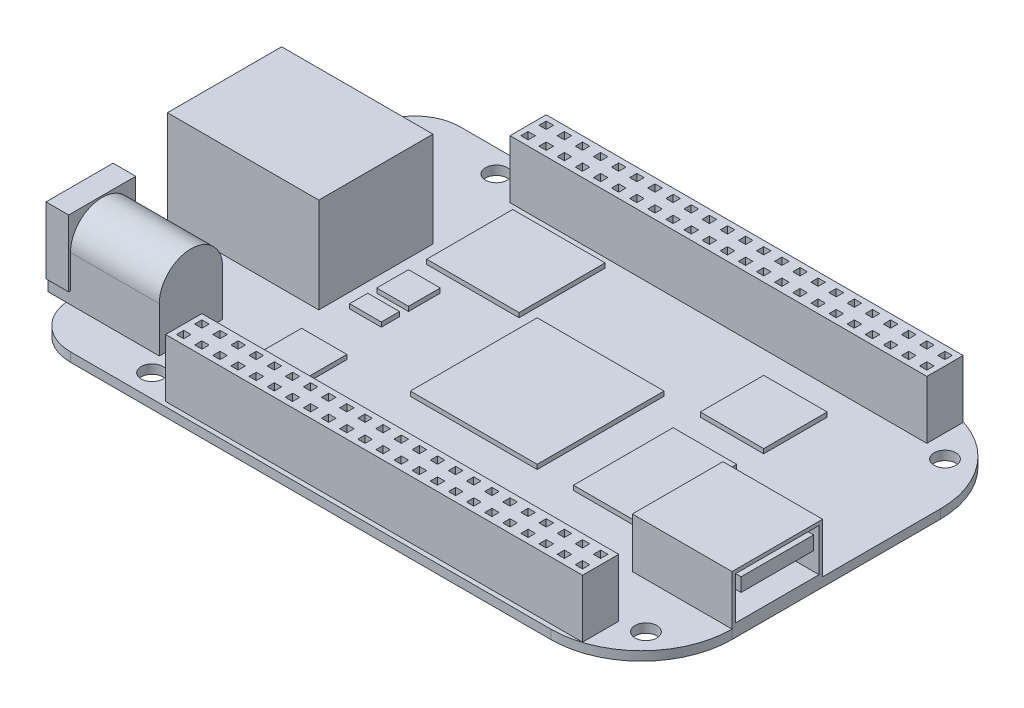
SolidWorks part; units mm, degrees
material "ABS"
ref_plane "Front Plane" through (0, 0, 0) normal (0, 0, 1) x (1, 0, 0)
ref_plane "Top Plane" through (0, 0, 0) normal (0, 1, 0) x (1, 0, 0)
ref_plane "Right Plane" through (0, 0, 0) normal (1, 0, 0) x (0, 0, -1)
sketch "Sketch1" plane through (0, 0, 0) normal (0, 1, 0) x (1, 0, 0)
  line L1 (-12.7, 0) -> (-80.01, 0)
  line L2 (0, 12.7) -> (0, 41.91)
  line L3 (-12.7, 54.61) -> (-80.01, 54.61)
  line L4 (-86.36, 6.35) -> (-86.36, 48.26)
  arc A0 (0, 12.7) -> (-12.7, 0) centre (-12.7, 12.7) cw
  arc A1 (0, 41.91) -> (-12.7, 54.61) centre (-12.7, 41.91) ccw
  arc A2 (-86.36, 6.35) -> (-80.01, 0) centre (-80.01, 6.35) ccw
  arc A3 (-86.36, 48.26) -> (-80.01, 54.61) centre (-80.01, 48.26) cw
  point P7 (0, 0)
  point P10 (0, 54.61)
  point P13 (-86.36, 0)
  dimension "D3" = 12.7
  dimension "D4" = 6.35
  dimension "D1" = 86.36
  dimension "D2" = 54.61
extrude "Boss-Extrude1" add sketch "Sketch1" along normal blind 1.27
sketch "Sketch2" plane through (0, 1.27, 0) normal (0, 1, 0) x (1, 0, 0)
  line L0 (-80.01, 0) -> (-12.7, 0) construction
  line L2 (-71.755, 51.435) -> (-71.755, 3.175) construction
  line L3 (-86.36, 48.26) -> (-86.36, 6.35) construction
  line L4 (-5.715, 48.26) -> (-5.715, 6.35) construction
  circle A0 centre (-71.755, 51.435) radius 1.524
  circle A1 centre (-71.755, 3.175) radius 1.524
  circle A2 centre (-5.715, 48.26) radius 1.524
  circle A3 centre (-5.715, 6.35) radius 1.524
  dimension "D7" = 3.048
  dimension "D1" = 48.26
  dimension "D2" = 41.91
  dimension "D3" = 6.35
  dimension "D4" = 14.605
  dimension "D5" = 80.645
  dimension "D6" = 3.175
extrude "Cut-Extrude1" cut sketch "Sketch2" along direction (0, -1, 0) on the side against the normal up to surface (1.27 mm away) up to face at (-44.4387, 0, -27.305)
sketch "Sketch3" plane through (0, 1.27, 0) normal (0, 1, 0) x (1, 0, 0)
  line L0 (-10.16, 48.895) -> (-10.16, 50.165) construction
  line L1 (-67.31, 53.975) -> (-8.89, 53.975)
  line L2 (-67.31, 53.975) -> (-67.31, 48.895)
  line L3 (-67.31, 48.895) -> (-8.89, 48.895)
  line L4 (-8.89, 53.975) -> (-8.89, 48.895)
  line L5 (-86.36, 27.305) -> (0, 27.305) construction
  line L6 (0, 12.7) -> (0, 41.91) construction
  line L7 (-66.548, 4.953) -> (-66.548, 3.937)
  line L8 (-66.548, 4.953) -> (-65.532, 4.953)
  line L9 (-10.16, 50.165) -> (-10.16, 52.705) construction
  line L10 (-10.16, 52.705) -> (-10.16, 53.975) construction
  line L11 (-13.208, 52.197) -> (-12.192, 52.197)
  line L12 (-10.668, 53.213) -> (-9.652, 53.213)
  line L13 (-10.668, 53.213) -> (-10.668, 52.197)
  line L14 (-10.668, 52.197) -> (-9.652, 52.197)
  line L15 (-9.652, 53.213) -> (-9.652, 52.197)
  line L16 (-10.668, 53.213) -> (-9.652, 52.197) construction
  line L17 (-10.668, 52.197) -> (-9.652, 53.213) construction
  line L18 (-10.668, 49.657) -> (-9.652, 49.657)
  line L19 (-10.668, 49.657) -> (-10.668, 50.673)
  line L20 (-10.668, 50.673) -> (-9.652, 50.673)
  line L21 (-9.652, 49.657) -> (-9.652, 50.673)
  line L22 (-10.668, 49.657) -> (-9.652, 50.673) construction
  line L23 (-10.668, 50.673) -> (-9.652, 49.657) construction
  line L24 (-13.208, 53.213) -> (-13.208, 52.197)
  line L25 (-13.208, 53.213) -> (-12.192, 53.213)
  line L26 (-12.192, 53.213) -> (-12.192, 52.197)
  line L27 (-13.208, 50.673) -> (-12.192, 50.673)
  line L28 (-12.192, 49.657) -> (-12.192, 50.673)
  line L29 (-13.208, 49.657) -> (-12.192, 49.657)
  line L30 (-13.208, 49.657) -> (-13.208, 50.673)
  line L31 (-15.748, 52.197) -> (-14.732, 52.197)
  line L32 (-15.748, 53.213) -> (-15.748, 52.197)
  line L33 (-15.748, 53.213) -> (-14.732, 53.213)
  line L34 (-14.732, 53.213) -> (-14.732, 52.197)
  line L35 (-15.748, 50.673) -> (-14.732, 50.673)
  line L36 (-14.732, 49.657) -> (-14.732, 50.673)
  line L37 (-15.748, 49.657) -> (-14.732, 49.657)
  line L38 (-15.748, 49.657) -> (-15.748, 50.673)
  line L39 (-18.288, 52.197) -> (-17.272, 52.197)
  line L40 (-18.288, 53.213) -> (-18.288, 52.197)
  line L41 (-18.288, 53.213) -> (-17.272, 53.213)
  line L42 (-17.272, 53.213) -> (-17.272, 52.197)
  line L43 (-18.288, 50.673) -> (-17.272, 50.673)
  line L44 (-17.272, 49.657) -> (-17.272, 50.673)
  line L45 (-18.288, 49.657) -> (-17.272, 49.657)
  line L46 (-18.288, 49.657) -> (-18.288, 50.673)
  line L47 (-20.828, 52.197) -> (-19.812, 52.197)
  line L48 (-20.828, 53.213) -> (-20.828, 52.197)
  line L49 (-20.828, 53.213) -> (-19.812, 53.213)
  line L50 (-19.812, 53.213) -> (-19.812, 52.197)
  line L51 (-20.828, 50.673) -> (-19.812, 50.673)
  line L52 (-19.812, 49.657) -> (-19.812, 50.673)
  line L53 (-20.828, 49.657) -> (-19.812, 49.657)
  line L54 (-20.828, 49.657) -> (-20.828, 50.673)
  line L55 (-23.368, 52.197) -> (-22.352, 52.197)
  line L56 (-23.368, 53.213) -> (-23.368, 52.197)
  line L57 (-23.368, 53.213) -> (-22.352, 53.213)
  line L58 (-22.352, 53.213) -> (-22.352, 52.197)
  line L59 (-23.368, 50.673) -> (-22.352, 50.673)
  line L60 (-22.352, 49.657) -> (-22.352, 50.673)
  line L61 (-23.368, 49.657) -> (-22.352, 49.657)
  line L62 (-23.368, 49.657) -> (-23.368, 50.673)
  line L63 (-25.908, 52.197) -> (-24.892, 52.197)
  line L64 (-25.908, 53.213) -> (-25.908, 52.197)
  line L65 (-25.908, 53.213) -> (-24.892, 53.213)
  line L66 (-24.892, 53.213) -> (-24.892, 52.197)
  line L67 (-25.908, 50.673) -> (-24.892, 50.673)
  line L68 (-24.892, 49.657) -> (-24.892, 50.673)
  line L69 (-25.908, 49.657) -> (-24.892, 49.657)
  line L70 (-25.908, 49.657) -> (-25.908, 50.673)
  line L71 (-28.448, 52.197) -> (-27.432, 52.197)
  line L72 (-28.448, 53.213) -> (-28.448, 52.197)
  line L73 (-28.448, 53.213) -> (-27.432, 53.213)
  line L74 (-27.432, 53.213) -> (-27.432, 52.197)
  line L75 (-28.448, 50.673) -> (-27.432, 50.673)
  line L76 (-27.432, 49.657) -> (-27.432, 50.673)
  line L77 (-28.448, 49.657) -> (-27.432, 49.657)
  line L78 (-28.448, 49.657) -> (-28.448, 50.673)
  line L79 (-30.988, 52.197) -> (-29.972, 52.197)
  line L80 (-30.988, 53.213) -> (-30.988, 52.197)
  line L81 (-30.988, 53.213) -> (-29.972, 53.213)
  line L82 (-29.972, 53.213) -> (-29.972, 52.197)
  line L83 (-30.988, 50.673) -> (-29.972, 50.673)
  line L84 (-29.972, 49.657) -> (-29.972, 50.673)
  line L85 (-30.988, 49.657) -> (-29.972, 49.657)
  line L86 (-30.988, 49.657) -> (-30.988, 50.673)
  line L87 (-33.528, 52.197) -> (-32.512, 52.197)
  line L88 (-33.528, 53.213) -> (-33.528, 52.197)
  line L89 (-33.528, 53.213) -> (-32.512, 53.213)
  line L90 (-32.512, 53.213) -> (-32.512, 52.197)
  line L91 (-33.528, 50.673) -> (-32.512, 50.673)
  line L92 (-32.512, 49.657) -> (-32.512, 50.673)
  line L93 (-33.528, 49.657) -> (-32.512, 49.657)
  line L94 (-33.528, 49.657) -> (-33.528, 50.673)
  line L95 (-36.068, 52.197) -> (-35.052, 52.197)
  line L96 (-36.068, 53.213) -> (-36.068, 52.197)
  line L97 (-36.068, 53.213) -> (-35.052, 53.213)
  line L98 (-35.052, 53.213) -> (-35.052, 52.197)
  line L99 (-36.068, 50.673) -> (-35.052, 50.673)
  line L100 (-35.052, 49.657) -> (-35.052, 50.673)
  line L101 (-36.068, 49.657) -> (-35.052, 49.657)
  line L102 (-36.068, 49.657) -> (-36.068, 50.673)
  line L103 (-38.608, 52.197) -> (-37.592, 52.197)
  line L104 (-38.608, 53.213) -> (-38.608, 52.197)
  line L105 (-38.608, 53.213) -> (-37.592, 53.213)
  line L106 (-37.592, 53.213) -> (-37.592, 52.197)
  line L107 (-38.608, 50.673) -> (-37.592, 50.673)
  line L108 (-37.592, 49.657) -> (-37.592, 50.673)
  line L109 (-38.608, 49.657) -> (-37.592, 49.657)
  line L110 (-38.608, 49.657) -> (-38.608, 50.673)
  line L111 (-41.148, 52.197) -> (-40.132, 52.197)
  line L112 (-41.148, 53.213) -> (-41.148, 52.197)
  line L113 (-41.148, 53.213) -> (-40.132, 53.213)
  line L114 (-40.132, 53.213) -> (-40.132, 52.197)
  line L115 (-41.148, 50.673) -> (-40.132, 50.673)
  line L116 (-40.132, 49.657) -> (-40.132, 50.673)
  line L117 (-41.148, 49.657) -> (-40.132, 49.657)
  line L118 (-41.148, 49.657) -> (-41.148, 50.673)
  line L119 (-43.688, 52.197) -> (-42.672, 52.197)
  line L120 (-43.688, 53.213) -> (-43.688, 52.197)
  line L121 (-43.688, 53.213) -> (-42.672, 53.213)
  line L122 (-42.672, 53.213) -> (-42.672, 52.197)
  line L123 (-43.688, 50.673) -> (-42.672, 50.673)
  line L124 (-42.672, 49.657) -> (-42.672, 50.673)
  line L125 (-43.688, 49.657) -> (-42.672, 49.657)
  line L126 (-43.688, 49.657) -> (-43.688, 50.673)
  line L127 (-46.228, 52.197) -> (-45.212, 52.197)
  line L128 (-46.228, 53.213) -> (-46.228, 52.197)
  line L129 (-46.228, 53.213) -> (-45.212, 53.213)
  line L130 (-45.212, 53.213) -> (-45.212, 52.197)
  line L131 (-46.228, 50.673) -> (-45.212, 50.673)
  line L132 (-45.212, 49.657) -> (-45.212, 50.673)
  line L133 (-46.228, 49.657) -> (-45.212, 49.657)
  line L134 (-46.228, 49.657) -> (-46.228, 50.673)
  line L135 (-48.768, 52.197) -> (-47.752, 52.197)
  line L136 (-48.768, 53.213) -> (-48.768, 52.197)
  line L137 (-48.768, 53.213) -> (-47.752, 53.213)
  line L138 (-47.752, 53.213) -> (-47.752, 52.197)
  line L139 (-48.768, 50.673) -> (-47.752, 50.673)
  line L140 (-47.752, 49.657) -> (-47.752, 50.673)
  line L141 (-48.768, 49.657) -> (-47.752, 49.657)
  line L142 (-48.768, 49.657) -> (-48.768, 50.673)
  line L143 (-51.308, 52.197) -> (-50.292, 52.197)
  line L144 (-51.308, 53.213) -> (-51.308, 52.197)
  line L145 (-51.308, 53.213) -> (-50.292, 53.213)
  line L146 (-50.292, 53.213) -> (-50.292, 52.197)
  line L147 (-51.308, 50.673) -> (-50.292, 50.673)
  line L148 (-50.292, 49.657) -> (-50.292, 50.673)
  line L149 (-51.308, 49.657) -> (-50.292, 49.657)
  line L150 (-51.308, 49.657) -> (-51.308, 50.673)
  line L151 (-53.848, 52.197) -> (-52.832, 52.197)
  line L152 (-53.848, 53.213) -> (-53.848, 52.197)
  line L153 (-53.848, 53.213) -> (-52.832, 53.213)
  line L154 (-52.832, 53.213) -> (-52.832, 52.197)
  line L155 (-53.848, 50.673) -> (-52.832, 50.673)
  line L156 (-52.832, 49.657) -> (-52.832, 50.673)
  line L157 (-53.848, 49.657) -> (-52.832, 49.657)
  line L158 (-53.848, 49.657) -> (-53.848, 50.673)
  line L159 (-56.388, 52.197) -> (-55.372, 52.197)
  line L160 (-56.388, 53.213) -> (-56.388, 52.197)
  line L161 (-56.388, 53.213) -> (-55.372, 53.213)
  line L162 (-55.372, 53.213) -> (-55.372, 52.197)
  line L163 (-56.388, 50.673) -> (-55.372, 50.673)
  line L164 (-55.372, 49.657) -> (-55.372, 50.673)
  line L165 (-56.388, 49.657) -> (-55.372, 49.657)
  line L166 (-56.388, 49.657) -> (-56.388, 50.673)
  line L167 (-58.928, 52.197) -> (-57.912, 52.197)
  line L168 (-58.928, 53.213) -> (-58.928, 52.197)
  line L169 (-58.928, 53.213) -> (-57.912, 53.213)
  line L170 (-57.912, 53.213) -> (-57.912, 52.197)
  line L171 (-58.928, 50.673) -> (-57.912, 50.673)
  line L172 (-57.912, 49.657) -> (-57.912, 50.673)
  line L173 (-58.928, 49.657) -> (-57.912, 49.657)
  line L174 (-58.928, 49.657) -> (-58.928, 50.673)
  line L175 (-61.468, 52.197) -> (-60.452, 52.197)
  line L176 (-61.468, 53.213) -> (-61.468, 52.197)
  line L177 (-61.468, 53.213) -> (-60.452, 53.213)
  line L178 (-60.452, 53.213) -> (-60.452, 52.197)
  line L179 (-61.468, 50.673) -> (-60.452, 50.673)
  line L180 (-60.452, 49.657) -> (-60.452, 50.673)
  line L181 (-61.468, 49.657) -> (-60.452, 49.657)
  line L182 (-61.468, 49.657) -> (-61.468, 50.673)
  line L183 (-64.008, 52.197) -> (-62.992, 52.197)
  line L184 (-64.008, 53.213) -> (-64.008, 52.197)
  line L185 (-64.008, 53.213) -> (-62.992, 53.213)
  line L186 (-62.992, 53.213) -> (-62.992, 52.197)
  line L187 (-64.008, 50.673) -> (-62.992, 50.673)
  line L188 (-62.992, 49.657) -> (-62.992, 50.673)
  line L189 (-64.008, 49.657) -> (-62.992, 49.657)
  line L190 (-64.008, 49.657) -> (-64.008, 50.673)
  line L191 (-66.548, 52.197) -> (-65.532, 52.197)
  line L192 (-66.548, 53.213) -> (-66.548, 52.197)
  line L193 (-66.548, 53.213) -> (-65.532, 53.213)
  line L194 (-65.532, 53.213) -> (-65.532, 52.197)
  line L195 (-66.548, 50.673) -> (-65.532, 50.673)
  line L196 (-65.532, 49.657) -> (-65.532, 50.673)
  line L197 (-66.548, 49.657) -> (-65.532, 49.657)
  line L198 (-66.548, 49.657) -> (-66.548, 50.673)
  line L199 (-66.548, 49.657) -> (-65.532, 50.673) construction
  line L200 (-86.36, 48.26) -> (-86.36, 6.35) construction
  line L201 (-65.532, 4.953) -> (-65.532, 3.937)
  line L202 (-12.7, 54.61) -> (-80.01, 54.61) construction
  line L203 (-66.548, 3.937) -> (-65.532, 3.937)
  line L204 (-65.532, 1.397) -> (-65.532, 2.413)
  line L205 (-66.548, 1.397) -> (-65.532, 1.397)
  line L206 (-66.548, 1.397) -> (-66.548, 2.413)
  line L207 (-66.548, 2.413) -> (-65.532, 2.413)
  line L208 (-64.008, 4.953) -> (-64.008, 3.937)
  line L209 (-64.008, 4.953) -> (-62.992, 4.953)
  line L210 (-62.992, 4.953) -> (-62.992, 3.937)
  line L211 (-64.008, 3.937) -> (-62.992, 3.937)
  line L212 (-62.992, 1.397) -> (-62.992, 2.413)
  line L213 (-64.008, 1.397) -> (-62.992, 1.397)
  line L214 (-64.008, 1.397) -> (-64.008, 2.413)
  line L215 (-64.008, 2.413) -> (-62.992, 2.413)
  line L216 (-61.468, 4.953) -> (-61.468, 3.937)
  line L217 (-61.468, 4.953) -> (-60.452, 4.953)
  line L218 (-60.452, 4.953) -> (-60.452, 3.937)
  line L219 (-61.468, 3.937) -> (-60.452, 3.937)
  line L220 (-60.452, 1.397) -> (-60.452, 2.413)
  line L221 (-61.468, 1.397) -> (-60.452, 1.397)
  line L222 (-61.468, 1.397) -> (-61.468, 2.413)
  line L223 (-61.468, 2.413) -> (-60.452, 2.413)
  line L224 (-58.928, 4.953) -> (-58.928, 3.937)
  line L225 (-58.928, 4.953) -> (-57.912, 4.953)
  line L226 (-57.912, 4.953) -> (-57.912, 3.937)
  line L227 (-58.928, 3.937) -> (-57.912, 3.937)
  line L228 (-57.912, 1.397) -> (-57.912, 2.413)
  line L229 (-58.928, 1.397) -> (-57.912, 1.397)
  line L230 (-58.928, 1.397) -> (-58.928, 2.413)
  line L231 (-58.928, 2.413) -> (-57.912, 2.413)
  line L232 (-56.388, 4.953) -> (-56.388, 3.937)
  line L233 (-56.388, 4.953) -> (-55.372, 4.953)
  line L234 (-55.372, 4.953) -> (-55.372, 3.937)
  line L235 (-56.388, 3.937) -> (-55.372, 3.937)
  line L236 (-55.372, 1.397) -> (-55.372, 2.413)
  line L237 (-56.388, 1.397) -> (-55.372, 1.397)
  line L238 (-56.388, 1.397) -> (-56.388, 2.413)
  line L239 (-56.388, 2.413) -> (-55.372, 2.413)
  line L240 (-53.848, 4.953) -> (-53.848, 3.937)
  line L241 (-53.848, 4.953) -> (-52.832, 4.953)
  line L242 (-52.832, 4.953) -> (-52.832, 3.937)
  line L243 (-53.848, 3.937) -> (-52.832, 3.937)
  line L244 (-52.832, 1.397) -> (-52.832, 2.413)
  line L245 (-53.848, 1.397) -> (-52.832, 1.397)
  line L246 (-53.848, 1.397) -> (-53.848, 2.413)
  line L247 (-53.848, 2.413) -> (-52.832, 2.413)
  line L248 (-51.308, 4.953) -> (-51.308, 3.937)
  line L249 (-51.308, 4.953) -> (-50.292, 4.953)
  line L250 (-50.292, 4.953) -> (-50.292, 3.937)
  line L251 (-51.308, 3.937) -> (-50.292, 3.937)
  line L252 (-50.292, 1.397) -> (-50.292, 2.413)
  line L253 (-51.308, 1.397) -> (-50.292, 1.397)
  line L254 (-51.308, 1.397) -> (-51.308, 2.413)
  line L255 (-51.308, 2.413) -> (-50.292, 2.413)
  line L256 (-48.768, 4.953) -> (-48.768, 3.937)
  line L257 (-48.768, 4.953) -> (-47.752, 4.953)
  line L258 (-47.752, 4.953) -> (-47.752, 3.937)
  line L259 (-48.768, 3.937) -> (-47.752, 3.937)
  line L260 (-47.752, 1.397) -> (-47.752, 2.413)
  line L261 (-48.768, 1.397) -> (-47.752, 1.397)
  line L262 (-48.768, 1.397) -> (-48.768, 2.413)
  line L263 (-48.768, 2.413) -> (-47.752, 2.413)
  line L264 (-46.228, 4.953) -> (-46.228, 3.937)
  line L265 (-46.228, 4.953) -> (-45.212, 4.953)
  line L266 (-45.212, 4.953) -> (-45.212, 3.937)
  line L267 (-46.228, 3.937) -> (-45.212, 3.937)
  line L268 (-45.212, 1.397) -> (-45.212, 2.413)
  line L269 (-46.228, 1.397) -> (-45.212, 1.397)
  line L270 (-46.228, 1.397) -> (-46.228, 2.413)
  line L271 (-46.228, 2.413) -> (-45.212, 2.413)
  line L272 (-43.688, 4.953) -> (-43.688, 3.937)
  line L273 (-43.688, 4.953) -> (-42.672, 4.953)
  line L274 (-42.672, 4.953) -> (-42.672, 3.937)
  line L275 (-43.688, 3.937) -> (-42.672, 3.937)
  line L276 (-42.672, 1.397) -> (-42.672, 2.413)
  line L277 (-43.688, 1.397) -> (-42.672, 1.397)
  line L278 (-43.688, 1.397) -> (-43.688, 2.413)
  line L279 (-43.688, 2.413) -> (-42.672, 2.413)
  line L280 (-41.148, 4.953) -> (-41.148, 3.937)
  line L281 (-41.148, 4.953) -> (-40.132, 4.953)
  line L282 (-40.132, 4.953) -> (-40.132, 3.937)
  line L283 (-41.148, 3.937) -> (-40.132, 3.937)
  line L284 (-40.132, 1.397) -> (-40.132, 2.413)
  line L285 (-41.148, 1.397) -> (-40.132, 1.397)
  line L286 (-41.148, 1.397) -> (-41.148, 2.413)
  line L287 (-41.148, 2.413) -> (-40.132, 2.413)
  line L288 (-38.608, 4.953) -> (-38.608, 3.937)
  line L289 (-38.608, 4.953) -> (-37.592, 4.953)
  line L290 (-37.592, 4.953) -> (-37.592, 3.937)
  line L291 (-38.608, 3.937) -> (-37.592, 3.937)
  line L292 (-37.592, 1.397) -> (-37.592, 2.413)
  line L293 (-38.608, 1.397) -> (-37.592, 1.397)
  line L294 (-38.608, 1.397) -> (-38.608, 2.413)
  line L295 (-38.608, 2.413) -> (-37.592, 2.413)
  line L296 (-36.068, 4.953) -> (-36.068, 3.937)
  line L297 (-36.068, 4.953) -> (-35.052, 4.953)
  line L298 (-35.052, 4.953) -> (-35.052, 3.937)
  line L299 (-36.068, 3.937) -> (-35.052, 3.937)
  line L300 (-35.052, 1.397) -> (-35.052, 2.413)
  line L301 (-36.068, 1.397) -> (-35.052, 1.397)
  line L302 (-36.068, 1.397) -> (-36.068, 2.413)
  line L303 (-36.068, 2.413) -> (-35.052, 2.413)
  line L304 (-33.528, 4.953) -> (-33.528, 3.937)
  line L305 (-33.528, 4.953) -> (-32.512, 4.953)
  line L306 (-32.512, 4.953) -> (-32.512, 3.937)
  line L307 (-33.528, 3.937) -> (-32.512, 3.937)
  line L308 (-32.512, 1.397) -> (-32.512, 2.413)
  line L309 (-33.528, 1.397) -> (-32.512, 1.397)
  line L310 (-33.528, 1.397) -> (-33.528, 2.413)
  line L311 (-33.528, 2.413) -> (-32.512, 2.413)
  line L312 (-30.988, 4.953) -> (-30.988, 3.937)
  line L313 (-30.988, 4.953) -> (-29.972, 4.953)
  line L314 (-29.972, 4.953) -> (-29.972, 3.937)
  line L315 (-30.988, 3.937) -> (-29.972, 3.937)
  line L316 (-29.972, 1.397) -> (-29.972, 2.413)
  line L317 (-30.988, 1.397) -> (-29.972, 1.397)
  line L318 (-30.988, 1.397) -> (-30.988, 2.413)
  line L319 (-30.988, 2.413) -> (-29.972, 2.413)
  line L320 (-28.448, 4.953) -> (-28.448, 3.937)
  line L321 (-28.448, 4.953) -> (-27.432, 4.953)
  line L322 (-27.432, 4.953) -> (-27.432, 3.937)
  line L323 (-28.448, 3.937) -> (-27.432, 3.937)
  line L324 (-27.432, 1.397) -> (-27.432, 2.413)
  line L325 (-28.448, 1.397) -> (-27.432, 1.397)
  line L326 (-28.448, 1.397) -> (-28.448, 2.413)
  line L327 (-28.448, 2.413) -> (-27.432, 2.413)
  line L328 (-25.908, 4.953) -> (-25.908, 3.937)
  line L329 (-25.908, 4.953) -> (-24.892, 4.953)
  line L330 (-24.892, 4.953) -> (-24.892, 3.937)
  line L331 (-25.908, 3.937) -> (-24.892, 3.937)
  line L332 (-24.892, 1.397) -> (-24.892, 2.413)
  line L333 (-25.908, 1.397) -> (-24.892, 1.397)
  line L334 (-25.908, 1.397) -> (-25.908, 2.413)
  line L335 (-25.908, 2.413) -> (-24.892, 2.413)
  line L336 (-23.368, 4.953) -> (-23.368, 3.937)
  line L337 (-23.368, 4.953) -> (-22.352, 4.953)
  line L338 (-22.352, 4.953) -> (-22.352, 3.937)
  line L339 (-23.368, 3.937) -> (-22.352, 3.937)
  line L340 (-22.352, 1.397) -> (-22.352, 2.413)
  line L341 (-23.368, 1.397) -> (-22.352, 1.397)
  line L342 (-23.368, 1.397) -> (-23.368, 2.413)
  line L343 (-23.368, 2.413) -> (-22.352, 2.413)
  line L344 (-20.828, 4.953) -> (-20.828, 3.937)
  line L345 (-20.828, 4.953) -> (-19.812, 4.953)
  line L346 (-19.812, 4.953) -> (-19.812, 3.937)
  line L347 (-20.828, 3.937) -> (-19.812, 3.937)
  line L348 (-19.812, 1.397) -> (-19.812, 2.413)
  line L349 (-20.828, 1.397) -> (-19.812, 1.397)
  line L350 (-20.828, 1.397) -> (-20.828, 2.413)
  line L351 (-20.828, 2.413) -> (-19.812, 2.413)
  line L352 (-18.288, 4.953) -> (-18.288, 3.937)
  line L353 (-18.288, 4.953) -> (-17.272, 4.953)
  line L354 (-17.272, 4.953) -> (-17.272, 3.937)
  line L355 (-18.288, 3.937) -> (-17.272, 3.937)
  line L356 (-17.272, 1.397) -> (-17.272, 2.413)
  line L357 (-18.288, 1.397) -> (-17.272, 1.397)
  line L358 (-18.288, 1.397) -> (-18.288, 2.413)
  line L359 (-18.288, 2.413) -> (-17.272, 2.413)
  line L360 (-15.748, 4.953) -> (-15.748, 3.937)
  line L361 (-15.748, 4.953) -> (-14.732, 4.953)
  line L362 (-14.732, 4.953) -> (-14.732, 3.937)
  line L363 (-15.748, 3.937) -> (-14.732, 3.937)
  line L364 (-14.732, 1.397) -> (-14.732, 2.413)
  line L365 (-15.748, 1.397) -> (-14.732, 1.397)
  line L366 (-15.748, 1.397) -> (-15.748, 2.413)
  line L367 (-15.748, 2.413) -> (-14.732, 2.413)
  line L368 (-13.208, 4.953) -> (-13.208, 3.937)
  line L369 (-13.208, 4.953) -> (-12.192, 4.953)
  line L370 (-12.192, 4.953) -> (-12.192, 3.937)
  line L371 (-13.208, 3.937) -> (-12.192, 3.937)
  line L372 (-12.192, 1.397) -> (-12.192, 2.413)
  line L373 (-13.208, 1.397) -> (-12.192, 1.397)
  line L374 (-13.208, 1.397) -> (-13.208, 2.413)
  line L375 (-9.652, 4.953) -> (-9.652, 3.937)
  line L376 (-10.668, 3.937) -> (-9.652, 3.937)
  line L377 (-10.668, 4.953) -> (-10.668, 3.937)
  line L378 (-10.668, 4.953) -> (-9.652, 4.953)
  line L379 (-9.652, 1.397) -> (-9.652, 2.413)
  line L380 (-10.668, 2.413) -> (-9.652, 2.413)
  line L381 (-10.668, 1.397) -> (-10.668, 2.413)
  line L382 (-10.668, 1.397) -> (-9.652, 1.397)
  line L383 (-13.208, 2.413) -> (-12.192, 2.413)
  line L384 (-8.89, 0.635) -> (-8.89, 5.715)
  line L385 (-67.31, 5.715) -> (-8.89, 5.715)
  line L386 (-67.31, 0.635) -> (-67.31, 5.715)
  line L387 (-67.31, 0.635) -> (-8.89, 0.635)
  circle A0 centre (-66.04, 50.165) radius 0.1361
  dimension "D1" = 1.016
  dimension "D2" = 2.54
  dimension "D3" = 5.08
  dimension "D4" = 58.42
  dimension "D5" = 1.27
  dimension "D7" = 20.32
  dimension "D8" = 0.635
  dimension "D6" = 23
extrude "Boss-Extrude2" add sketch "Sketch3" along normal blind 8.128 contours L4 L1 L2 L3 L193 L194 L191 L192 L185 L186 L183 L184 L177 L178 L175 L176 L169 L170 L167 L168 L161 L162 L159 L160 L153 L154 L151 L152 L145 L146 L143 L144 L137 L138 L135 L136 L129 L130 L127 L128 L121 | L386 L387 L384 L385 L374 L383 L372 L373 L382 L381 L380 L379 L366 L367 L364 L365 L363 L360 L361 L362 L350 L351 L348 L349 L347 L344 L345 L346 L334 L335 L332 L333 L331 L328 L329 L330 L318 L319 L316 L317 L315 region at (-38.1, 1.27, -51.435) region at (-38.1, 1.27, -3.175)
sketch "Sketch4" plane through (0, 1.27, 0) normal (0, 1, 0) x (1, 0, 0)
  line L0 (-86.36, 48.26) -> (-86.36, 6.35) construction
  line L1 (-67.691, 22.479) -> (-88.9, 22.479)
  line L2 (-67.691, 22.479) -> (-67.691, 38.481)
  line L3 (-67.691, 38.481) -> (-88.9, 38.481)
  line L4 (-88.9, 22.479) -> (-88.9, 38.481)
  line L5 (-12.7, 54.61) -> (-80.01, 54.61) construction
  dimension "D1" = 2.54
  dimension "D2" = 21.209
  dimension "D3" = 16.002
  dimension "D4" = 16.129
extrude "Boss-Extrude3" add sketch "Sketch4" along normal blind 13.335
sketch "Sketch5" plane through (-88.9, 0, 0) normal (-1, 0, 0) x (0, 0, 1)
  line L0 (-30.48, 2.286) -> (-30.48, 3.937) construction
  line L1 (-36.83, 12.065) -> (-24.13, 12.065)
  line L2 (-36.83, 12.065) -> (-36.83, 5.461)
  line L3 (-36.83, 5.461) -> (-24.13, 5.461)
  line L4 (-24.13, 12.065) -> (-24.13, 5.461)
  line L5 (-33.655, 5.461) -> (-27.305, 5.461)
  line L6 (-33.655, 5.461) -> (-33.655, 3.937)
  line L7 (-33.655, 3.937) -> (-27.305, 3.937)
  line L8 (-27.305, 5.461) -> (-27.305, 3.937)
  line L9 (-32.512, 3.937) -> (-28.448, 3.937)
  line L10 (-32.512, 3.937) -> (-32.512, 2.286)
  line L11 (-32.512, 2.286) -> (-28.448, 2.286)
  line L12 (-28.448, 3.937) -> (-28.448, 2.286)
  line L13 (-30.48, 3.937) -> (-30.48, 5.461) construction
  line L14 (-38.481, 14.605) -> (-22.479, 14.605) construction
  line L15 (-36.83, 12.065) -> (-38.481, 12.065) construction
  line L16 (-38.481, 14.605) -> (-38.481, 1.27) construction
  line L17 (-24.13, 12.065) -> (-22.479, 12.065) construction
  line L18 (-22.479, 14.605) -> (-22.479, 1.27) construction
  dimension "D1" = 12.7
  dimension "D2" = 6.604
  dimension "D3" = 2.54
  dimension "D4" = 1.524
  dimension "D5" = 1.651
  dimension "D6" = 4.064
  dimension "D7" = 6.35
extrude "Cut-Extrude2" cut sketch "Sketch5" against normal blind 17.78 contours L4 L1 L2 L3 | L8 L3 L6 L7 | L12 L7 L10 L11 region at (-88.9, 8.763, -30.48) region at (-88.9, 4.699, -30.48) region at (-88.9, 3.1115, -30.48)
sketch "Sketch6" plane through (0, 1.27, 0) normal (0, 1, 0) x (1, 0, 0)
  line L0 (-67.31, 48.895) -> (-8.89, 48.895) construction
  line L1 (-65.659, 35.56) -> (-52.705, 35.56)
  line L2 (-65.659, 35.56) -> (-65.659, 47.625)
  line L3 (-65.659, 47.625) -> (-52.705, 47.625)
  line L4 (-52.705, 35.56) -> (-52.705, 47.625)
  line L5 (-50.8, 36.195) -> (-33.02, 36.195)
  line L6 (-50.8, 36.195) -> (-50.8, 18.415)
  line L7 (-50.8, 18.415) -> (-33.02, 18.415)
  line L8 (-33.02, 36.195) -> (-33.02, 18.415)
  line L9 (-27.94, 45.085) -> (-19.05, 45.085)
  line L10 (-27.94, 45.085) -> (-27.94, 36.195)
  line L11 (-27.94, 36.195) -> (-19.05, 36.195)
  line L12 (-19.05, 45.085) -> (-19.05, 36.195)
  line L13 (-27.94, 32.385) -> (-19.05, 32.385)
  line L14 (-27.94, 32.385) -> (-27.94, 18.415)
  line L15 (-27.94, 18.415) -> (-19.05, 18.415)
  line L16 (-19.05, 32.385) -> (-19.05, 18.415)
  line L17 (-66.04, 18.415) -> (-59.69, 18.415)
  line L18 (-66.04, 18.415) -> (-66.04, 12.065)
  line L19 (-66.04, 12.065) -> (-59.69, 12.065)
  line L20 (-59.69, 18.415) -> (-59.69, 12.065)
  line L21 (-65.659, 27.305) -> (-61.214, 27.305)
  line L22 (-65.659, 27.305) -> (-65.659, 24.765)
  line L23 (-65.659, 24.765) -> (-61.214, 24.765)
  line L24 (-61.214, 27.305) -> (-61.214, 24.765)
  line L25 (-65.659, 33.02) -> (-61.214, 33.02)
  line L26 (-65.659, 33.02) -> (-65.659, 28.575)
  line L27 (-65.659, 28.575) -> (-61.214, 28.575)
  line L28 (-61.214, 33.02) -> (-61.214, 28.575)
  line L29 (0, 12.7) -> (0, 41.91) construction
  line L30 (-67.31, 48.895) -> (-8.89, 48.895) construction
  line L31 (-67.31, 5.715) -> (-8.89, 5.715) construction
  line L33 (-67.31, 0.635) -> (-67.31, 5.715) construction
  dimension "D1" = 8.89
  dimension "D2" = 13.97
  dimension "D3" = 3.81
  dimension "D4" = 3.81
  dimension "D5" = 19.05
  dimension "D6" = 17.78
  dimension "D7" = 12.7
  dimension "D8" = 33.02
  dimension "D9" = 12.954
  dimension "D10" = 12.065
  dimension "D11" = 1.905
  dimension "D12" = 4.445
  dimension "D13" = 2.54
  dimension "D14" = 1.27
  dimension "D15" = 2.54
  dimension "D16" = 1.27
  dimension "D17" = 6.35
  dimension "D18" = 6.35
  dimension "D19" = 1.27
extrude "Boss-Extrude4" add sketch "Sketch6" along normal blind 0.635
sketch "Sketch7" plane through (0, 1.27, 0) normal (0, 1, 0) x (1, 0, 0)
  line L1 (0, 12.7) -> (-13.97, 12.7)
  line L2 (0, 12.7) -> (0, 25.4)
  line L3 (0, 25.4) -> (-13.97, 25.4)
  line L4 (-13.97, 12.7) -> (-13.97, 25.4)
  line L5 (-80.01, 0) -> (-12.7, 0) construction
  line L6 (0, 12.7) -> (0, 41.91) construction
  dimension "D1" = 12.7
  dimension "D2" = 13.97
  dimension "D3" = 25.4
extrude "Boss-Extrude5" add sketch "Sketch7" along normal blind 6.985
sketch "Sketch8" plane through (0, 0, 0) normal (1, 0, 0) x (0, 0, -1)
  line L0 (12.7, 8.255) -> (25.4, 8.255) construction
  line L1 (13.97, 6.985) -> (24.13, 6.985)
  line L2 (13.97, 6.985) -> (13.97, 5.08)
  line L3 (13.97, 5.08) -> (24.13, 5.08)
  line L4 (24.13, 6.985) -> (24.13, 5.08)
  line L5 (13.208, 7.747) -> (24.892, 7.747)
  line L6 (13.208, 7.747) -> (13.208, 1.778)
  line L7 (13.208, 1.778) -> (24.892, 1.778)
  line L8 (24.892, 7.747) -> (24.892, 1.778)
  line L9 (25.4, 8.255) -> (25.4, 1.27) construction
  line L10 (12.7, 8.255) -> (12.7, 1.27) construction
  line L11 (12.7, 1.27) -> (0, 1.27) construction
  line L12 (13.97, 7.18) -> (13.208, 7.18) construction
  line L14 (24.892, 6.9479) -> (24.13, 6.9479) construction
  dimension "D1" = 0.508
  dimension "D2" = 0.508
  dimension "D3" = 0.508
  dimension "D4" = 0.508
  dimension "D5" = 1.905
  dimension "D6" = 10.16
  dimension "D7" = 3.175
extrude "Cut-Extrude3" cut sketch "Sketch8" against normal blind 12.7
sketch "Sketch9" plane through (0, 1.27, 0) normal (0, 1, 0) x (1, 0, 0)
  line L0 (-88.9, 38.481) -> (-88.9, 22.479) construction
  line L1 (-73.279, 5.715) -> (-88.9, 5.715)
  line L2 (-73.279, 5.715) -> (-73.279, 14.605)
  line L3 (-73.279, 14.605) -> (-88.9, 14.605)
  line L4 (-88.9, 5.715) -> (-88.9, 14.605)
  line L5 (-67.31, 5.715) -> (-8.89, 5.715) construction
  circle A0 centre (-71.755, 3.175) radius 1.524 construction
  dimension "D1" = 8.89
extrude "Boss-Extrude6" add sketch "Sketch9" along normal blind 6.35
sketch "Sketch10" plane through (-88.9, 0, 0) normal (-1, 0, 0) x (0, 0, 1)
  line L0 (-14.605, 7.62) -> (-5.715, 7.62) construction
  circle A0 centre (-10.16, 7.62) radius 4.445
  circle A1 centre (-10.16, 7.62) radius 3.4925
  circle A2 centre (-10.16, 7.62) radius 0.635
  line M3 (-5.715, 7.62) -> (-14.605, 7.62)
  dimension "D1" = 1.27
  dimension "D2" = 6.985
extrude "Boss-Extrude7" add sketch "Sketch10" along direction (1, 0, 0) on the side against the normal up to surface (15.621 mm away) contours A1 A0 M3 | A1 A0 M3 | A2 M3 | A2 A1 M3 region at (-88.9, 7.7194, -6.1912) region at (-88.9, 3.2744, -10.16) region at (-88.9, 9.1437, -10.16) region at (-88.9, 7.8895, -10.16) up to face at (-73.279, 4.445, -10.16)
sketch "Sketch11" plane through (-88.9, 0, 0) normal (-1, 0, 0) x (0, 0, 1)
  line L0 (-14.605, 7.62) -> (-14.605, 1.27) construction
  line L1 (-5.461, 2.952) -> (-14.859, 2.952)
  line L2 (-5.461, 2.952) -> (-5.461, 12.288)
  line L3 (-5.461, 12.288) -> (-14.859, 12.288)
  line L4 (-14.859, 2.952) -> (-14.859, 12.288)
  line L5 (-5.461, 2.952) -> (-14.859, 12.288) construction
  line L6 (-5.461, 12.288) -> (-14.859, 2.952) construction
  point P0 (-10.16, 7.62)
  dimension "D1" = 0.254
extrude "Boss-Extrude8" add sketch "Sketch11" against normal blind 3.175
extrude "Cut-Extrude4" cut sketch "Sketch10<3>" against normal blind 12.7 contours A2 A1 M3 | A2 A1 M3 region at (-88.9, 9.1437, -10.16) region at (-88.9, 6.0963, -10.16)
sketch "Sketch10<3>" plane through (-88.9, 0, 0) normal (-1, 0, 0) x (0, 0, 1) same geometry as "Sketch10"
fillet "Fillet1" radius 0.635 1 edges at (-88.9, 7.62, -9.525)
ref_plane "평면1" through (0, 0, -27.305) normal (0, 0, 1) x (1, 0, 0)
